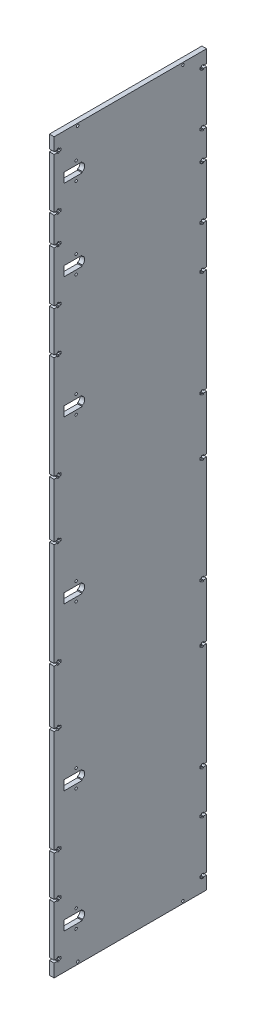
SolidWorks part; units mm, degrees
material "Acrylic (Medium-high impact)"
ref_plane "Front Plane" through (0, 0, 0) normal (0, 0, 1) x (1, 0, 0)
ref_plane "Top Plane" through (0, 0, 0) normal (0, 1, 0) x (1, 0, 0)
ref_plane "Right Plane" through (0, 0, 0) normal (1, 0, 0) x (0, 0, -1)
sketch "Sketch1" plane through (0, 0, 0) normal (1, 0, 0) x (0, 0, -1)
  line L0 (0, 100) -> (188.4, 100) construction
  line L1 (0, 0) -> (188.4, 0)
  line L2 (0, 0) -> (0, 900)
  line L3 (0, 900) -> (188.4, 900)
  line L4 (188.4, 0) -> (188.4, 900)
  line L5 (94.2, 900) -> (94.2, 0) construction
  line L6 (0, 450) -> (188.4, 450) construction
  line L7 (0, 300) -> (188.4, 300) construction
  line L8 (0, 500) -> (188.4, 500) construction
  line L9 (0, 700) -> (188.4, 700) construction
  line L10 (0, 800) -> (188.4, 800) construction
  line L11 (0, 850) -> (188.4, 850) construction
  line L12 (0, 750) -> (188.4, 750) construction
  line L13 (0, 600) -> (188.4, 600) construction
  line L14 (0, 400) -> (188.4, 400) construction
  line L15 (0, 200) -> (188.4, 200) construction
  line L16 (0, 50) -> (188.4, 50) construction
  line L29 (6.35, 884) -> (6.35, 885.21)
  line L30 (8.35, 881) -> (8.35, 884)
  line L31 (6.35, 884) -> (8.35, 884)
  line L32 (6.35, 881) -> (8.35, 881)
  line L33 (6.35, 879.79) -> (6.35, 881)
  line L34 (4, 885.21) -> (6.35, 885.21)
  line L35 (4, 879.79) -> (4, 881)
  line L36 (4, 879.79) -> (6.35, 879.79)
  line L37 (4, 884) -> (4, 885.21)
  line L38 (0, 884) -> (4, 884)
  line L39 (0, 881) -> (0, 884)
  line L40 (0, 881) -> (4, 881)
  line L41 (0, 819) -> (4, 819)
  line L42 (0, 819) -> (0, 816)
  line L43 (0, 816) -> (4, 816)
  line L44 (4, 816) -> (4, 814.79)
  line L45 (4, 820.21) -> (6.35, 820.21)
  line L46 (4, 820.21) -> (4, 819)
  line L47 (4, 814.79) -> (6.35, 814.79)
  line L48 (6.35, 820.21) -> (6.35, 819)
  line L49 (6.35, 819) -> (8.35, 819)
  line L50 (6.35, 816) -> (8.35, 816)
  line L51 (8.35, 819) -> (8.35, 816)
  line L52 (6.35, 816) -> (6.35, 814.79)
  line L53 (6.35, 784) -> (6.35, 785.21)
  line L54 (8.35, 781) -> (8.35, 784)
  line L55 (6.35, 784) -> (8.35, 784)
  line L56 (6.35, 781) -> (8.35, 781)
  line L57 (6.35, 779.79) -> (6.35, 781)
  line L58 (4, 785.21) -> (6.35, 785.21)
  line L59 (4, 779.79) -> (4, 781)
  line L60 (4, 779.79) -> (6.35, 779.79)
  line L61 (4, 784) -> (4, 785.21)
  line L62 (0, 784) -> (4, 784)
  line L63 (0, 781) -> (0, 784)
  line L64 (0, 781) -> (4, 781)
  line L65 (0, 719) -> (4, 719)
  line L66 (0, 719) -> (0, 716)
  line L67 (0, 716) -> (4, 716)
  line L68 (4, 716) -> (4, 714.79)
  line L69 (4, 720.21) -> (6.35, 720.21)
  line L70 (4, 720.21) -> (4, 719)
  line L71 (4, 714.79) -> (6.35, 714.79)
  line L72 (6.35, 720.21) -> (6.35, 719)
  line L73 (6.35, 719) -> (8.35, 719)
  line L74 (6.35, 716) -> (8.35, 716)
  line L75 (8.35, 719) -> (8.35, 716)
  line L76 (6.35, 716) -> (6.35, 714.79)
  line L77 (6.35, 666.5) -> (6.35, 667.71)
  line L78 (8.35, 663.5) -> (8.35, 666.5)
  line L79 (6.35, 666.5) -> (8.35, 666.5)
  line L80 (6.35, 663.5) -> (8.35, 663.5)
  line L81 (6.35, 662.29) -> (6.35, 663.5)
  line L82 (4, 667.71) -> (6.35, 667.71)
  line L83 (4, 662.29) -> (4, 663.5)
  line L84 (4, 662.29) -> (6.35, 662.29)
  line L85 (4, 666.5) -> (4, 667.71)
  line L86 (0, 666.5) -> (4, 666.5)
  line L87 (0, 663.5) -> (4, 663.5)
  line L88 (0, 666.5) -> (0, 663.5)
  line L89 (0, 533.5) -> (0, 536.5)
  line L90 (0, 536.5) -> (4, 536.5)
  line L91 (0, 533.5) -> (4, 533.5)
  line L92 (4, 533.5) -> (4, 532.29)
  line L93 (4, 537.71) -> (6.35, 537.71)
  line L94 (4, 537.71) -> (4, 536.5)
  line L95 (4, 532.29) -> (6.35, 532.29)
  line L96 (6.35, 537.71) -> (6.35, 536.5)
  line L97 (6.35, 536.5) -> (8.35, 536.5)
  line L98 (6.35, 533.5) -> (8.35, 533.5)
  line L99 (8.35, 536.5) -> (8.35, 533.5)
  line L100 (6.35, 533.5) -> (6.35, 532.29)
  line L101 (0, 336.5) -> (4, 336.5)
  line L102 (0, 333.5) -> (4, 333.5)
  line L103 (4, 333.5) -> (4, 332.29)
  line L104 (4, 337.71) -> (6.35, 337.71)
  line L105 (4, 337.71) -> (4, 336.5)
  line L106 (4, 332.29) -> (6.35, 332.29)
  line L107 (6.35, 337.71) -> (6.35, 336.5)
  line L108 (6.35, 336.5) -> (8.35, 336.5)
  line L109 (6.35, 333.5) -> (8.35, 333.5)
  line L110 (8.35, 336.5) -> (8.35, 333.5)
  line L111 (6.35, 333.5) -> (6.35, 332.29)
  line L112 (6.35, 466.5) -> (6.35, 467.71)
  line L113 (8.35, 463.5) -> (8.35, 466.5)
  line L114 (6.35, 466.5) -> (8.35, 466.5)
  line L115 (6.35, 463.5) -> (8.35, 463.5)
  line L116 (6.35, 462.29) -> (6.35, 463.5)
  line L117 (4, 467.71) -> (6.35, 467.71)
  line L118 (4, 462.29) -> (4, 463.5)
  line L119 (4, 462.29) -> (6.35, 462.29)
  line L120 (4, 466.5) -> (4, 467.71)
  line L121 (0, 466.5) -> (4, 466.5)
  line L122 (0, 463.5) -> (4, 463.5)
  line L123 (0, 136.5) -> (4, 136.5)
  line L124 (0, 133.5) -> (4, 133.5)
  line L125 (4, 133.5) -> (4, 132.29)
  line L126 (4, 137.71) -> (6.35, 137.71)
  line L127 (4, 137.71) -> (4, 136.5)
  line L128 (4, 132.29) -> (6.35, 132.29)
  line L129 (6.35, 137.71) -> (6.35, 136.5)
  line L130 (6.35, 136.5) -> (8.35, 136.5)
  line L131 (6.35, 133.5) -> (8.35, 133.5)
  line L132 (8.35, 136.5) -> (8.35, 133.5)
  line L133 (6.35, 133.5) -> (6.35, 132.29)
  line L134 (6.35, 266.5) -> (6.35, 267.71)
  line L135 (8.35, 263.5) -> (8.35, 266.5)
  line L136 (6.35, 266.5) -> (8.35, 266.5)
  line L137 (6.35, 263.5) -> (8.35, 263.5)
  line L138 (6.35, 262.29) -> (6.35, 263.5)
  line L139 (4, 267.71) -> (6.35, 267.71)
  line L140 (4, 262.29) -> (4, 263.5)
  line L141 (4, 262.29) -> (6.35, 262.29)
  line L142 (4, 266.5) -> (4, 267.71)
  line L143 (0, 266.5) -> (4, 266.5)
  line L144 (0, 263.5) -> (4, 263.5)
  line L145 (6.35, 84) -> (6.35, 85.21)
  line L146 (8.35, 81) -> (8.35, 84)
  line L147 (6.35, 84) -> (8.35, 84)
  line L148 (6.35, 81) -> (8.35, 81)
  line L149 (6.35, 79.79) -> (6.35, 81)
  line L150 (4, 85.21) -> (6.35, 85.21)
  line L151 (4, 79.79) -> (4, 81)
  line L152 (4, 79.79) -> (6.35, 79.79)
  line L153 (4, 84) -> (4, 85.21)
  line L154 (0, 84) -> (4, 84)
  line L155 (0, 81) -> (4, 81)
  line L156 (0, 19) -> (4, 19)
  line L157 (0, 16) -> (4, 16)
  line L158 (4, 16) -> (4, 14.79)
  line L159 (4, 20.21) -> (6.35, 20.21)
  line L160 (4, 20.21) -> (4, 19)
  line L161 (4, 14.79) -> (6.35, 14.79)
  line L162 (6.35, 20.21) -> (6.35, 19)
  line L163 (6.35, 19) -> (8.35, 19)
  line L164 (6.35, 16) -> (8.35, 16)
  line L165 (8.35, 19) -> (8.35, 16)
  line L166 (6.35, 16) -> (6.35, 14.79)
  line L167 (0, 81) -> (0, 31.2711) construction
  line L168 (182.05, 16) -> (182.05, 14.79)
  line L169 (180.05, 19) -> (180.05, 16)
  line L170 (182.05, 16) -> (180.05, 16)
  line L171 (182.05, 19) -> (180.05, 19)
  line L172 (182.05, 20.21) -> (182.05, 19)
  line L173 (184.4, 14.79) -> (182.05, 14.79)
  line L174 (184.4, 20.21) -> (184.4, 19)
  line L175 (184.4, 20.21) -> (182.05, 20.21)
  line L176 (184.4, 16) -> (184.4, 14.79)
  line L177 (188.4, 16) -> (184.4, 16)
  line L178 (188.4, 19) -> (184.4, 19)
  line L179 (188.4, 81) -> (184.4, 81)
  line L180 (188.4, 84) -> (184.4, 84)
  line L181 (184.4, 84) -> (184.4, 85.21)
  line L182 (184.4, 79.79) -> (182.05, 79.79)
  line L183 (184.4, 79.79) -> (184.4, 81)
  line L184 (184.4, 85.21) -> (182.05, 85.21)
  line L185 (182.05, 79.79) -> (182.05, 81)
  line L186 (182.05, 81) -> (180.05, 81)
  line L187 (182.05, 84) -> (180.05, 84)
  line L188 (180.05, 81) -> (180.05, 84)
  line L189 (182.05, 84) -> (182.05, 85.21)
  line L190 (182.05, 133.5) -> (182.05, 132.29)
  line L191 (180.05, 136.5) -> (180.05, 133.5)
  line L192 (182.05, 133.5) -> (180.05, 133.5)
  line L193 (182.05, 136.5) -> (180.05, 136.5)
  line L194 (182.05, 137.71) -> (182.05, 136.5)
  line L195 (184.4, 132.29) -> (182.05, 132.29)
  line L196 (184.4, 137.71) -> (184.4, 136.5)
  line L197 (184.4, 137.71) -> (182.05, 137.71)
  line L198 (184.4, 133.5) -> (184.4, 132.29)
  line L199 (188.4, 133.5) -> (184.4, 133.5)
  line L200 (188.4, 136.5) -> (184.4, 136.5)
  line L201 (188.4, 263.5) -> (184.4, 263.5)
  line L202 (188.4, 266.5) -> (184.4, 266.5)
  line L203 (184.4, 266.5) -> (184.4, 267.71)
  line L204 (184.4, 262.29) -> (182.05, 262.29)
  line L205 (184.4, 262.29) -> (184.4, 263.5)
  line L206 (184.4, 267.71) -> (182.05, 267.71)
  line L207 (182.05, 262.29) -> (182.05, 263.5)
  line L208 (182.05, 263.5) -> (180.05, 263.5)
  line L209 (182.05, 266.5) -> (180.05, 266.5)
  line L210 (180.05, 263.5) -> (180.05, 266.5)
  line L211 (182.05, 266.5) -> (182.05, 267.71)
  line L212 (182.05, 333.5) -> (182.05, 332.29)
  line L213 (180.05, 336.5) -> (180.05, 333.5)
  line L214 (182.05, 333.5) -> (180.05, 333.5)
  line L215 (182.05, 336.5) -> (180.05, 336.5)
  line L216 (182.05, 337.71) -> (182.05, 336.5)
  line L217 (184.4, 332.29) -> (182.05, 332.29)
  line L218 (184.4, 337.71) -> (184.4, 336.5)
  line L219 (184.4, 337.71) -> (182.05, 337.71)
  line L220 (184.4, 333.5) -> (184.4, 332.29)
  line L221 (188.4, 333.5) -> (184.4, 333.5)
  line L222 (188.4, 336.5) -> (184.4, 336.5)
  line L223 (188.4, 463.5) -> (184.4, 463.5)
  line L224 (188.4, 466.5) -> (184.4, 466.5)
  line L225 (184.4, 466.5) -> (184.4, 467.71)
  line L226 (184.4, 462.29) -> (182.05, 462.29)
  line L227 (184.4, 462.29) -> (184.4, 463.5)
  line L228 (184.4, 467.71) -> (182.05, 467.71)
  line L229 (182.05, 462.29) -> (182.05, 463.5)
  line L230 (182.05, 463.5) -> (180.05, 463.5)
  line L231 (182.05, 466.5) -> (180.05, 466.5)
  line L232 (180.05, 463.5) -> (180.05, 466.5)
  line L233 (182.05, 466.5) -> (182.05, 467.71)
  line L234 (182.05, 533.5) -> (182.05, 532.29)
  line L235 (180.05, 536.5) -> (180.05, 533.5)
  line L236 (182.05, 533.5) -> (180.05, 533.5)
  line L237 (182.05, 536.5) -> (180.05, 536.5)
  line L238 (182.05, 537.71) -> (182.05, 536.5)
  line L239 (184.4, 532.29) -> (182.05, 532.29)
  line L240 (184.4, 537.71) -> (184.4, 536.5)
  line L241 (184.4, 537.71) -> (182.05, 537.71)
  line L242 (184.4, 533.5) -> (184.4, 532.29)
  line L243 (188.4, 533.5) -> (184.4, 533.5)
  line L244 (188.4, 536.5) -> (184.4, 536.5)
  line L245 (188.4, 663.5) -> (184.4, 663.5)
  line L246 (188.4, 666.5) -> (184.4, 666.5)
  line L247 (184.4, 666.5) -> (184.4, 667.71)
  line L248 (184.4, 662.29) -> (182.05, 662.29)
  line L249 (184.4, 662.29) -> (184.4, 663.5)
  line L250 (184.4, 667.71) -> (182.05, 667.71)
  line L251 (182.05, 662.29) -> (182.05, 663.5)
  line L252 (182.05, 663.5) -> (180.05, 663.5)
  line L253 (182.05, 666.5) -> (180.05, 666.5)
  line L254 (180.05, 663.5) -> (180.05, 666.5)
  line L255 (182.05, 666.5) -> (182.05, 667.71)
  line L256 (182.05, 716) -> (182.05, 714.79)
  line L257 (180.05, 719) -> (180.05, 716)
  line L258 (182.05, 716) -> (180.05, 716)
  line L259 (182.05, 719) -> (180.05, 719)
  line L260 (182.05, 720.21) -> (182.05, 719)
  line L261 (184.4, 714.79) -> (182.05, 714.79)
  line L262 (184.4, 720.21) -> (184.4, 719)
  line L263 (184.4, 720.21) -> (182.05, 720.21)
  line L264 (184.4, 716) -> (184.4, 714.79)
  line L265 (188.4, 716) -> (184.4, 716)
  line L266 (188.4, 719) -> (184.4, 719)
  line L267 (188.4, 781) -> (184.4, 781)
  line L268 (188.4, 784) -> (184.4, 784)
  line L269 (184.4, 784) -> (184.4, 785.21)
  line L270 (184.4, 779.79) -> (182.05, 779.79)
  line L271 (184.4, 779.79) -> (184.4, 781)
  line L272 (184.4, 785.21) -> (182.05, 785.21)
  line L273 (182.05, 779.79) -> (182.05, 781)
  line L274 (182.05, 781) -> (180.05, 781)
  line L275 (182.05, 784) -> (180.05, 784)
  line L276 (180.05, 781) -> (180.05, 784)
  line L277 (182.05, 784) -> (182.05, 785.21)
  line L278 (182.05, 816) -> (182.05, 814.79)
  line L279 (180.05, 819) -> (180.05, 816)
  line L280 (182.05, 816) -> (180.05, 816)
  line L281 (182.05, 819) -> (180.05, 819)
  line L282 (182.05, 820.21) -> (182.05, 819)
  line L283 (184.4, 814.79) -> (182.05, 814.79)
  line L284 (184.4, 820.21) -> (184.4, 819)
  line L285 (184.4, 820.21) -> (182.05, 820.21)
  line L286 (184.4, 816) -> (184.4, 814.79)
  line L287 (188.4, 816) -> (184.4, 816)
  line L288 (188.4, 819) -> (184.4, 819)
  line L289 (188.4, 881) -> (184.4, 881)
  line L290 (188.4, 884) -> (184.4, 884)
  line L291 (184.4, 884) -> (184.4, 885.21)
  line L292 (184.4, 879.79) -> (182.05, 879.79)
  line L293 (184.4, 879.79) -> (184.4, 881)
  line L294 (184.4, 885.21) -> (182.05, 885.21)
  line L295 (182.05, 879.79) -> (182.05, 881)
  line L296 (182.05, 881) -> (180.05, 881)
  line L297 (182.05, 884) -> (180.05, 884)
  line L298 (180.05, 881) -> (180.05, 884)
  line L299 (182.05, 884) -> (182.05, 885.21)
  line L300 (27.221, 861) -> (27.221, 839) construction
  line L301 (12.141, 850) -> (0, 850) construction
  line L302 (12.141, 844.025) -> (34.691, 844.025)
  line L303 (12.141, 855.975) -> (12.141, 844.025)
  line L304 (34.691, 855.975) -> (12.141, 855.975)
  line L305 (34.691, 844.025) -> (34.691, 855.975)
  line L312 (12.141, 744.025) -> (34.691, 744.025)
  line L313 (34.691, 755.975) -> (12.141, 755.975)
  line L314 (12.141, 755.975) -> (12.141, 744.025)
  line L315 (34.691, 744.025) -> (34.691, 755.975)
  line L316 (27.221, 761) -> (27.221, 739) construction
  line L317 (12.141, 750) -> (0, 750) construction
  line L318 (12.141, 594.025) -> (34.691, 594.025)
  line L319 (34.691, 605.975) -> (12.141, 605.975)
  line L320 (12.141, 605.975) -> (12.141, 594.025)
  line L321 (34.691, 594.025) -> (34.691, 605.975)
  line L322 (27.221, 611) -> (27.221, 589) construction
  line L323 (12.141, 600) -> (0, 600) construction
  line L324 (12.141, 44.025) -> (34.691, 44.025)
  line L325 (34.691, 55.975) -> (12.141, 55.975)
  line L326 (12.141, 55.975) -> (12.141, 44.025)
  line L327 (34.691, 44.025) -> (34.691, 55.975)
  line L328 (27.221, 61) -> (27.221, 39) construction
  line L329 (12.141, 50) -> (0, 50) construction
  line L330 (12.141, 194.025) -> (34.691, 194.025)
  line L331 (34.691, 205.975) -> (12.141, 205.975)
  line L332 (12.141, 205.975) -> (12.141, 194.025)
  line L333 (34.691, 194.025) -> (34.691, 205.975)
  line L334 (27.221, 211) -> (27.221, 189) construction
  line L335 (12.141, 200) -> (0, 200) construction
  line L336 (12.141, 394.025) -> (34.691, 394.025)
  line L337 (34.691, 405.975) -> (12.141, 405.975)
  line L338 (12.141, 405.975) -> (12.141, 394.025)
  line L339 (34.691, 394.025) -> (34.691, 405.975)
  line L340 (27.221, 411) -> (27.221, 389) construction
  line L341 (12.141, 400) -> (0, 400) construction
  circle A0 centre (27.221, 861) radius 1.5
  circle A1 centre (27.221, 839) radius 1.5
  circle A4 centre (27.221, 761) radius 1.5
  circle A5 centre (27.221, 739) radius 1.5
  circle A6 centre (27.221, 611) radius 1.5
  circle A7 centre (27.221, 589) radius 1.5
  circle A8 centre (27.221, 61) radius 1.5
  circle A9 centre (27.221, 39) radius 1.5
  circle A10 centre (27.221, 211) radius 1.5
  circle A11 centre (27.221, 189) radius 1.5
  circle A12 centre (27.221, 411) radius 1.5
  circle A13 centre (27.221, 389) radius 1.5
  point P51 (8.35, 882.5)
  point P102 (8.35, 665)
  point P120 (94.2, 450)
  point P326 (8.35, 82.5)
  dimension "D1" = 900
  dimension "D2" = 188.4
  dimension "D3" = 100
  dimension "D4" = 100
  dimension "D5" = 200
  dimension "D6" = 200
  dimension "D7" = 200
  dimension "D8" = 50
  dimension "D9" = 100
  dimension "D10" = 100
  dimension "D11" = 100
  dimension "D12" = 50
  dimension "D13" = 50
  dimension "D14" = 4
  dimension "D15" = 2.35
  dimension "D16" = 2
  dimension "D17" = 4
  dimension "D18" = 2.35
  dimension "D19" = 2
  dimension "D20" = 5.42
  dimension "D21" = 3
  dimension "D22" = 32.5
  dimension "D23" = 65
  dimension "D24" = 3
  dimension "D25" = 5.42
  dimension "D26" = 3
  dimension "D27" = 32.5
extrude "Boss-Extrude1" add sketch "Sketch1" along normal blind 5.8 contours L297 L299 L294 L291 L290 L4 L3 L2 L38 L37 L34 L29 L31 L30 L32 L33 L36 L35 L40 L41 L46 L45 L48 L49 L51 L50 L52 L47 L44 L43 L62 L61 L58 L53 L55 L54 L56 L57 L60 L59 L64 L65 L70 L69 L72 L73 L75 L74 region at (0, 449.6351, -94.9188)
sketch "Sketch2" plane through (5.8, 0, 0) normal (1, 0, 0) x (0, 0, -1)
  line L0 (94.2, 900) -> (94.2, 0) construction
  line L1 (0, 900) -> (188.4, 900) construction
  line L2 (0, 0) -> (188.4, 0) construction
  line L3 (94.2, 450) -> (188.4, 450) construction
  line L4 (188.4, 336.5) -> (188.4, 463.5) construction
  circle A0 centre (159.2, 897.1) radius 1.55
  circle A1 centre (29.2, 897.1) radius 1.55
  circle A2 centre (159.2, 2.9) radius 1.55
  circle A3 centre (29.2, 2.9) radius 1.55
  dimension "D3" = 3.1
  dimension "D1" = 65
  dimension "D2" = 2.9
extrude "Cut-Extrude1" cut sketch "Sketch2" against normal up to surface (5.8 mm away) up to face at (0, 189, -28.721)
sketch "Sketch3" plane through (5.8, 0, 0) normal (1, 0, 0) x (0, 0, -1)
  line L0 (34.691, 745.5) -> (34.691, 754.5)
  line L1 (34.691, 44.025) -> (34.691, 55.975) construction
  line L2 (34.691, 844.025) -> (34.691, 855.975) construction
  line L3 (34.691, 845.5) -> (34.691, 854.5)
  line L4 (34.691, 595.5) -> (34.691, 604.5)
  line L5 (34.691, 395.5) -> (34.691, 404.5)
  line L6 (34.691, 195.5) -> (34.691, 204.5)
  line L7 (34.691, 45.5) -> (34.691, 54.5)
  line L8 (34.691, 194.025) -> (34.691, 205.975) construction
  line L9 (34.691, 394.025) -> (34.691, 405.975) construction
  line L10 (34.691, 594.025) -> (34.691, 605.975) construction
  line L11 (34.691, 744.025) -> (34.691, 755.975) construction
  ellipse E0 centre (34.691, 850) end of major axis (34.691, 854.5) minor radius 3 (34.691, 854.5) -> (34.691, 845.5) cw
  ellipse E1 centre (34.691, 750) end of major axis (34.691, 754.5) minor radius 3 (34.691, 754.5) -> (34.691, 745.5) cw
  ellipse E2 centre (34.691, 600) end of major axis (34.691, 604.5) minor radius 3 (34.691, 604.5) -> (34.691, 595.5) cw
  ellipse E3 centre (34.691, 400) end of major axis (34.691, 404.5) minor radius 3 (34.691, 404.5) -> (34.691, 395.5) cw
  ellipse E4 centre (34.691, 200) end of major axis (34.691, 195.5) minor radius 3 (34.691, 204.5) -> (34.691, 195.5) cw
  ellipse E5 centre (34.691, 50) end of major axis (34.691, 54.5) minor radius 3 (34.691, 54.5) -> (34.691, 45.5) cw
  point P47 (34.691, 50)
  dimension "D1" = 3
  dimension "D2" = 9
  dimension "D3" = 3
  dimension "D4" = 9
  dimension "D5" = 3
  dimension "D6" = 9
  dimension "D7" = 3
  dimension "D8" = 9
  dimension "D9" = 3
  dimension "D10" = 9
  dimension "D11" = 3
  dimension "D12" = 9
extrude "Cut-Extrude2" cut sketch "Sketch3" against normal up to surface (5.8 mm away) up to face at (0, 897.1, -30.75)
